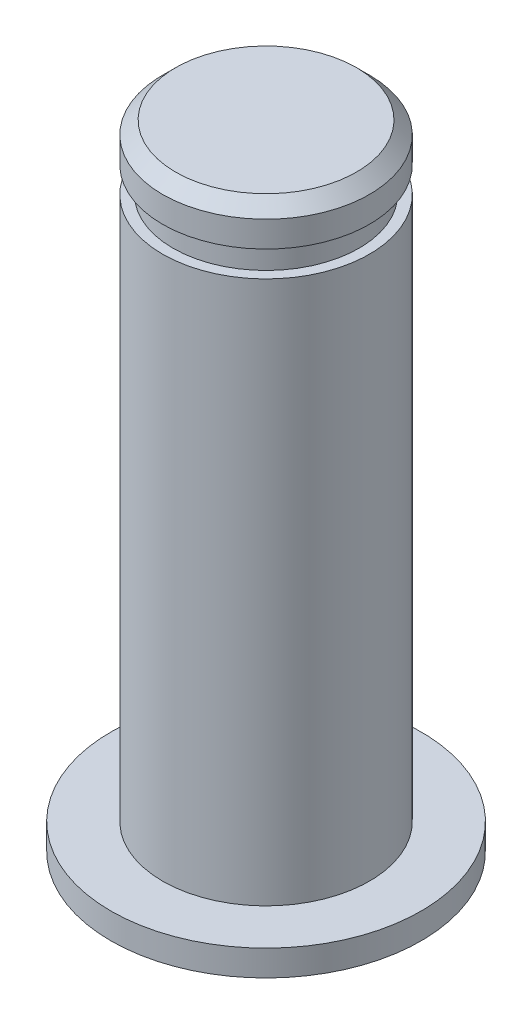
SolidWorks part; units mm, degrees
ref_plane "Спереди" through (0, 0, 0) normal (0, 0, 1) x (1, 0, 0)
ref_plane "Сверху" through (0, 0, 0) normal (0, 1, 0) x (1, 0, 0)
ref_plane "Справа" through (0, 0, 0) normal (1, 0, 0) x (0, 0, -1)
sketch "Эскиз1" plane through (0, 0, 0) normal (0, 0, 1) x (1, 0, 0)
  line L0 (-4, 24.5) -> (0, 24.5)
  line L1 (0, 24.5) -> (0, 0)
  line L2 (0, 0) -> (-6, 0)
  line L3 (-6, 0) -> (-6, 1)
  line L4 (-6, 1) -> (-4, 1)
  line L5 (-4, 1) -> (-4, 22)
  line L6 (-4, 22) -> (-3.6, 22)
  line L7 (-3.6, 22) -> (-3.6, 23)
  line L8 (-3.6, 23) -> (-4, 23)
  line L9 (-4, 23) -> (-4, 24.5)
  line L10 (0, 0) -> (0, -50000) construction
  line L12 (4, 22) -> (-4, 22) construction
  line L13 (4, 22) -> (-4, 22) construction
  line L14 (4, 22) -> (-4, 22) construction
  line L16 (3.6, 23) -> (-3.6, 23) construction
  line L18 (3.6, 23) -> (-3.6, 23) construction
  point P4 (0, 0)
  point P15 (0, 0)
  point P16 (0, 0)
  point P17 (0, 0)
  point P21 (0, 0)
  point P22 (0, 0)
  point P23 (0, 0)
  point P24 (0, 0)
  point P25 (0, 0)
  point P26 (0, 0)
  point P27 (0, 0)
  dimension "D1" = 1.5
  dimension "D2" = 2
  dimension "D3" = 1
revolve "Повернуть1" add sketch "Эскиз1" angle 360 about L10
chamfer "Фаска1" distance 0.5 angle 45 1 edges at (0, 24.5, 4)
